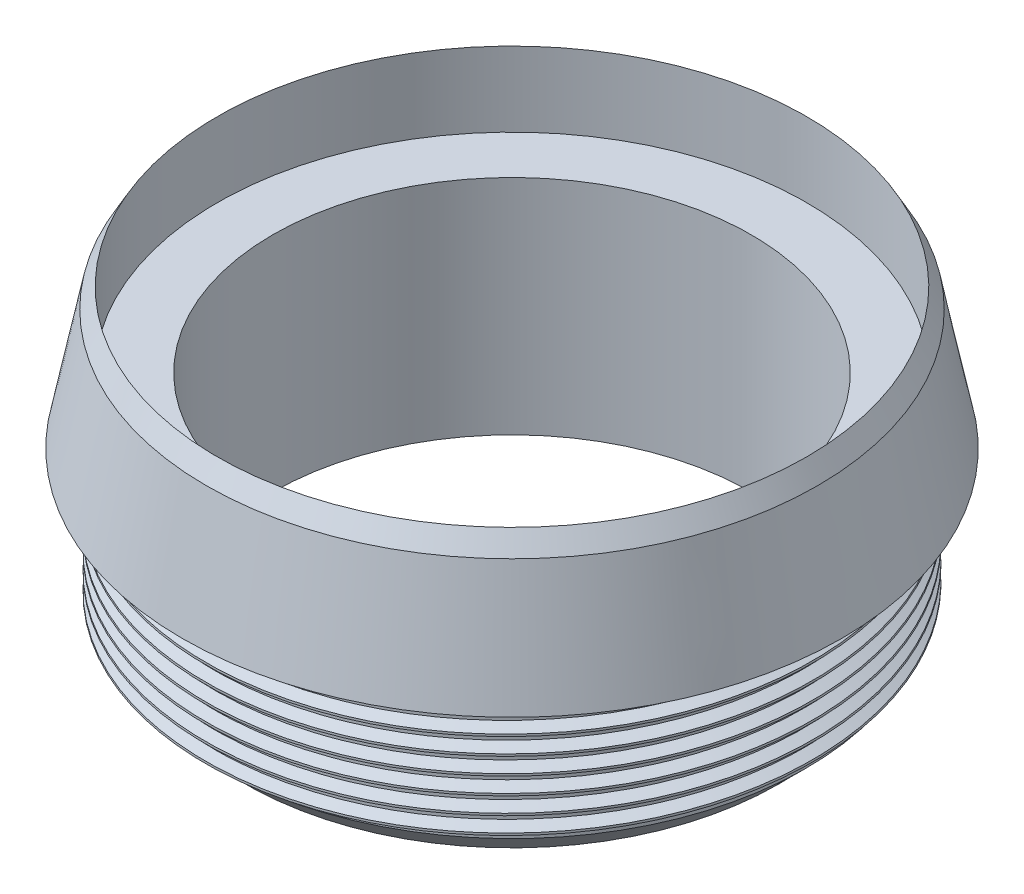
SolidWorks part; units mm, degrees
ref_plane "Front Plane" through (0, 0, 0) normal (0, 0, 1) x (1, 0, 0)
ref_plane "Top Plane" through (0, 0, 0) normal (0, 1, 0) x (1, 0, 0)
ref_plane "Right Plane" through (0, 0, 0) normal (1, 0, 0) x (0, 0, -1)
sketch "Sketch1" plane through (0, 0, 0) normal (0, 0, 1) x (1, 0, 0)
  line L0 (0, -527.2215) -> (0, 25833.8527) construction
  line L2 (-21.45, -9.5337) -> (-21.45, 1.9663)
  line L5 (-21.45, 1.9663) -> (-24.05, 1.9663)
  line L19 (-17.45, 6.7256) -> (-17.45, -9.5337)
  line L22 (-21.45, -9.5337) -> (-17.45, -9.5337)
  line L24 (-22.2953, 10.7397) -> (-21.5, 12.1635)
  line L26 (-21.5, 6.7256) -> (-17.45, 6.7256)
  line L29 (-22.2953, 10.7397) -> (-24.05, 1.9663)
  line L30 (-21.5, 12.1635) -> (-21.5, 6.7256)
  point P7 (0, 0)
  point P12 (0, 0)
  dimension "D2" = 11.5
  dimension "D7" = 48.1
revolve "Revolve1" add sketch "Sketch1" angle 360 about L0
thread "Thread1" pitch 1.25 method extrude profile "Thread Profile1" start angle 0, offset 0, length 9, pitch 1.25, diameter 42.9
ref_plane "Plane1" through (-21.45, 1.9663, 0) normal (0, 0, 1) x (-1, 0, 0)
sketch "Thread Profile1" plane through (-21.45, 1.9663, 0) normal (0, 0, 1) x (-1, 0, 0)
  line L0 (0, 0) -> (0, 1.25) construction
  line L1 (0, 0) -> (0.6766, 0.3906)
  line L2 (0.6766, 0.3906) -> (0.6766, 0.5469)
  line L3 (0.6766, 0.5469) -> (0, 0.9375)
  line L4 (0.6766, 0.4687) -> (0, 0.4687) construction
  line L11 (0, 0) -> (0, 0.9375)
  point P2 (0, 0)
  dimension "Pitch" = 1.25
  dimension "Profile_Angle" = 60
  dimension "Profile_Land" = 0.1562
  dimension "Profile_Height" = 0.6766
fillet "Chamfer1" radius 2 1 edges at (21.45, -9.5337, 0) type face fillet profile chamfer first side face at (21.45, -9.5337, 0) second side face at (17.45, -9.5337, 0)
